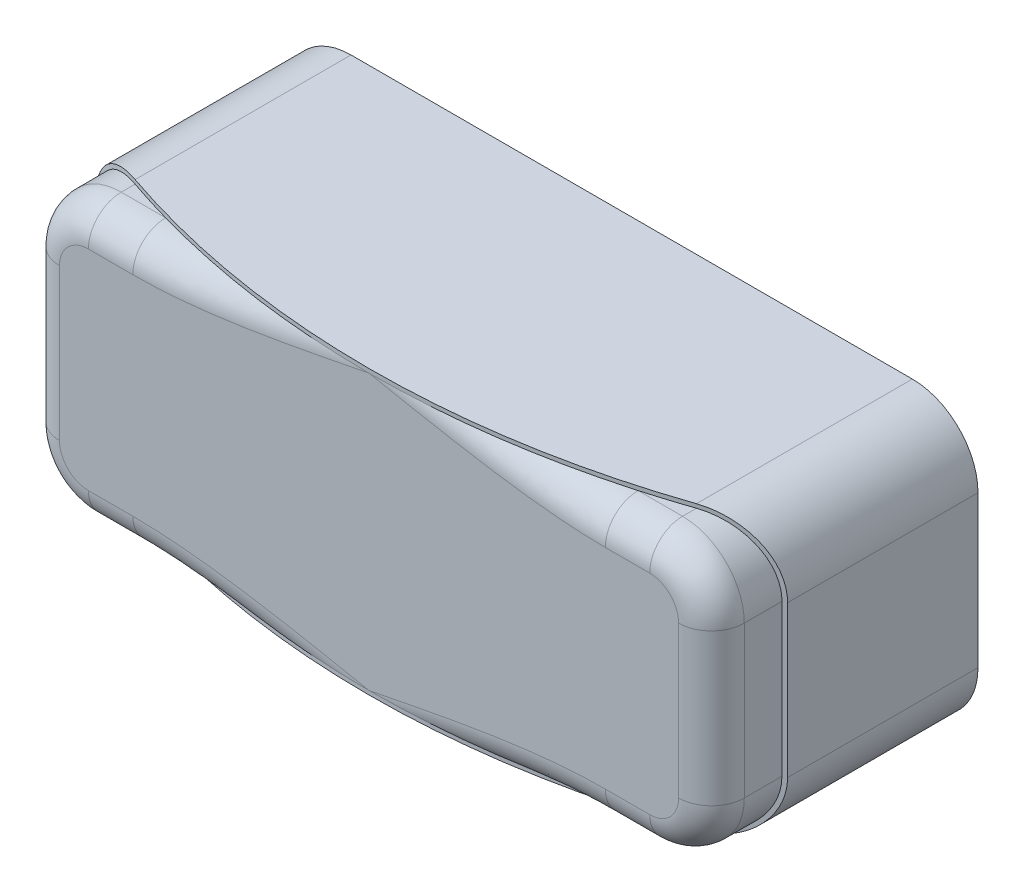
SolidWorks part; units mm, degrees
ref_plane "Front Plane" through (0, 0, 0) normal (0, 0, 1) x (1, 0, 0)
ref_plane "Top Plane" through (0, 0, 0) normal (0, 1, 0) x (1, 0, 0)
ref_plane "Right Plane" through (0, 0, 0) normal (1, 0, 0) x (0, 0, -1)
sketch "Sketch1" plane through (0, 0, 0) normal (0, 0, 1) x (1, 0, 0)
  line L0 (-105.5, 43.065) -> (105.5, -43.065) construction
  line L1 (-85.5, 43.065) -> (85.5, 43.065)
  line L2 (-105.5, 23.065) -> (-105.5, -23.065)
  line L3 (-85.5, -43.065) -> (85.5, -43.065)
  line L4 (105.5, 23.065) -> (105.5, -23.065)
  arc A0 (85.5, -43.065) -> (105.5, -23.065) centre (85.5, -23.065) ccw
  arc A1 (85.5, 43.065) -> (105.5, 23.065) centre (85.5, 23.065) cw
  arc A2 (-105.5, -23.065) -> (-85.5, -43.065) centre (-85.5, -23.065) ccw
  arc A3 (-85.5, 43.065) -> (-105.5, 23.065) centre (-85.5, 23.065) ccw
  point P11 (105.5, 43.065)
  dimension "D3" = 20
  dimension "D1" = 86.13
  dimension "D2" = 211
extrude "Boss-Extrude1" add sketch "Sketch1" against normal blind 80
sketch "Sketch2" plane through (0, 43.065, 0) normal (0, 1, 0) x (1, 0, 0)
  line L0 (105.5, 80) -> (105.5, 0) construction
  line L1 (-105.5, 80) -> (-105.5, 0) construction
  line L2 (85.5, 0) -> (-85.5, 0) construction
  line L4 (85.5, 0) -> (105.5, 0) construction
  line L5 (-105.5, 0) -> (-85.5, 0) construction
  line L6 (105.5, 80) -> (105.5, 0)
  line L7 (85.5, 0) -> (105.5, 0)
  line L8 (85.5, 0) -> (-85.5, 0)
  line L9 (-105.5, 0) -> (-85.5, 0)
  line L10 (-105.5, 80) -> (-105.5, 0)
  arc A0 (-105.5, 22) -> (105.5, 22) centre (0, 263.9602) ccw
  point P3 (0, 0)
  point P4 (0, 0)
  point P7 (0, 0)
  point P10 (0, 0)
  point P11 (0, 0)
  point P14 (-105.5, 18.8542)
  line M1 (-85.5, 0) -> (85.5, 0)
  line M2 (85.5, 0) -> (85.5, 80)
  line M4 (-85.5, 80) -> (-85.5, 0)
  dimension "D1" = 22
extrude "Cut-Extrude1" cut sketch "Sketch2" against normal through all contours A0 L10 L9 M4 | A0 M4 M1 | A0 L8 M2 | A0 L7 L6 M2
sketch "Sketch3" plane through (0, 0, 0) normal (0, 0, 1) x (1, 0, 0)
  line L8 (-85.5, -41.865) -> (85.5, -41.865)
  line L9 (104.3, -23.065) -> (104.3, 23.065)
  line L10 (85.5, 41.865) -> (-85.5, 41.865)
  line L11 (-104.3, 23.065) -> (-104.3, -23.065)
  line L12 (-85.5, -41.865) -> (85.5, -41.865)
  line L13 (104.3, -23.065) -> (104.3, 23.065)
  line L14 (85.5, 41.865) -> (-85.5, 41.865)
  line L15 (-104.3, 23.065) -> (-104.3, -23.065)
  arc A8 (85.5, -41.865) -> (104.3, -23.065) centre (85.5, -23.065) ccw
  arc A9 (104.3, 23.065) -> (85.5, 41.865) centre (85.5, 23.065) ccw
  arc A10 (-85.5, 41.865) -> (-104.3, 23.065) centre (-85.5, 23.065) ccw
  arc A11 (-104.3, -23.065) -> (-85.5, -41.865) centre (-85.5, -23.065) ccw
  arc A12 (85.5, -41.865) -> (104.3, -23.065) centre (85.5, -23.065) ccw
  arc A13 (104.3, 23.065) -> (85.5, 41.865) centre (85.5, 23.065) ccw
  arc A14 (-85.5, 41.865) -> (-104.3, 23.065) centre (-85.5, 23.065) ccw
  arc A15 (-104.3, -23.065) -> (-85.5, -41.865) centre (-85.5, -23.065) ccw
  dimension "D1" = 1.2
extrude "Boss-Extrude2" add sketch "Sketch3" against normal up to body separate body
fillet "Fillet1" radius 10 10 edges at (-98.7936, 36.3586, 0) (-42.75, 41.865, 0) (42.75, 41.865, 0) (98.7936, 36.3586, 0) (104.3, 0, 0) (98.7936, -36.3586, 0) (42.75, -41.865, 0) (-42.75, -41.865, 0) (-98.7936, -36.3586, 0) (-104.3, 0, 0)
